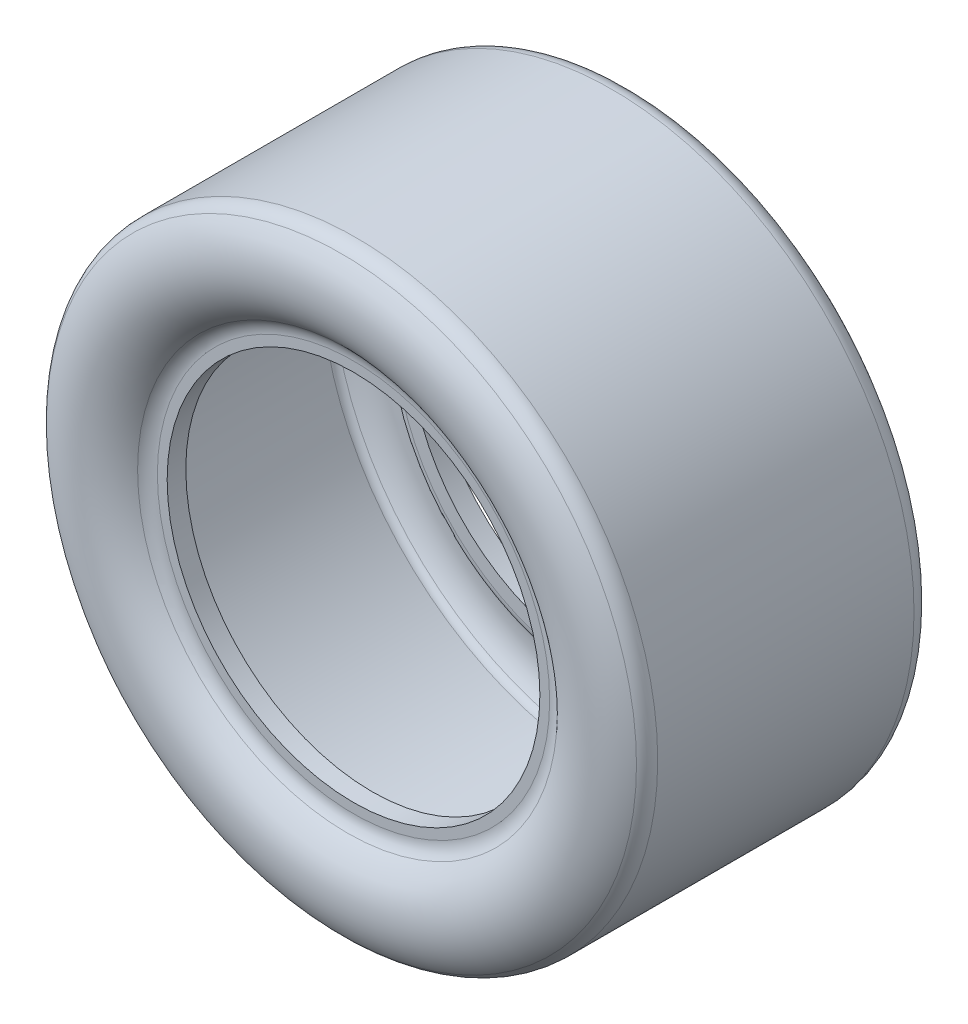
SolidWorks part; units mm, degrees
material "Tire Rubber"
ref_plane "X-Z Datum" through (0, 0, 0) normal (0, 0, 1) x (1, 0, 0)
ref_plane "X-Y Datum" through (0, 0, 0) normal (0, 1, 0) x (1, 0, 0)
ref_plane "Y-Z Plane" through (0, 0, 0) normal (1, 0, 0) x (0, 0, -1)
sketch "Sketch1" plane through (0, 0, 0) normal (1, 0, 0) x (0, 0, -1)
  line L0 (0, 0) -> (-132272.0706, 0) construction
  line L1 (-92.71, 205.74) -> (92.71, 205.74)
  line L2 (0, 0) -> (0, -132272.0706) construction
  line L4 (-88.9, 127) -> (-88.9, 139.7)
  line L5 (88.9, 127) -> (88.9, 139.7)
  line L6 (-88.9, 127) -> (-76.2, 127)
  line L8 (76.2, 127) -> (88.9, 127)
  line L9 (-76.2, 127) -> (-76.2, 136.7746)
  line L10 (76.2, 127) -> (76.2, 136.7746)
  line L11 (-86.5663, 197.8025) -> (86.5663, 197.8025)
  arc A2 (-92.71, 205.74) -> (-88.9, 139.7) centre (-64.4017, 174.2433) ccw
  arc A3 (92.71, 205.74) -> (88.9, 139.7) centre (64.4017, 174.2433) cw
  arc A4 (-91.5819, 195.3468) -> (-80.4384, 143.7974) centre (-64.4017, 174.2433) ccw
  arc A5 (-86.5663, 197.8025) -> (-91.5819, 195.3468) centre (-86.5663, 191.4525) ccw
  arc A6 (-76.2, 136.7746) -> (-80.4384, 143.7974) centre (-84.1375, 136.7746) ccw
  arc A7 (91.5819, 195.3468) -> (80.4384, 143.7974) centre (64.4017, 174.2433) cw
  arc A8 (86.5663, 197.8025) -> (91.5819, 195.3468) centre (86.5663, 191.4525) cw
  arc A9 (80.4384, 143.7974) -> (76.2, 136.7746) centre (84.1375, 136.7746) ccw
  point P7 (-106.68, 171.8041)
  dimension "D4" = 213.36
  dimension "D9" = 7.9375
  dimension "D10" = 6.35
  dimension "D11" = 7.9375
  dimension "D12" = 7.9375
  dimension "D1" = 185.42
  dimension "D2" = 411.48
  dimension "D3" = 12.7
  dimension "D5" = 177.8
  dimension "D6" = 254
  dimension "D7" = 12.7
  dimension "D8" = 7.9375
revolve "Revolve1" add sketch "Sketch1" angle 360 about L0
fillet "Fillet1" radius 12.7 4 edges at (-139.7, 0, -88.9) (-139.7, 0, 88.9) (-205.74, 0, -92.71) (-205.74, 0, 92.71)
ref_axis "Axis1" [suppressed] through (0, 0, 87.3303) along (0, 0, -1)
sketch "Sketch2" plane through (0, 0, 0) normal (0, 0, 1) x (1, 0, 0)
  circle A0 centre (0, 0) radius 205.74
  dimension "D1" = 411.48
extrude "Boss-Extrude1" [suppressed] add sketch "Sketch2" along normal mid plane 185.42
fillet "Fillet2" [suppressed] radius 25.4
sketch "Sketch3" plane through (0, 0, 0) normal (1, 0, 0) x (0, 0, -1)
  line L0 (0, 0) -> (0, 170833.7536) construction
  line L1 (0, 0) -> (-170833.7536, 0) construction
  line L2 (106.68, 205.74) -> (-106.68, 205.74)
  line L3 (-106.68, 205.74) -> (-106.68, 0)
  line L4 (106.68, 205.74) -> (106.68, 0)
  line L5 (106.68, 0) -> (-106.68, 0)
  point P7 (0, 205.74)
  dimension "D1" = 213.36
  dimension "D2" = 411.48
revolve "Revolve2" [suppressed] add sketch "Sketch3" angle 360 about L1
ref_plane "Plane1" through (0, 0, 0) normal (0, 0, 1) x (1, 0, 0)
sketch "Sketch4" plane through (0, 0, 0) normal (0, 0, 1) x (1, 0, 0)
  line L0 (0, 0) -> (0, 96.3997) construction
move or copy body "Body-Move/Copy2" [suppressed] bodies to move or copy 101
move or copy body "Body-Move/Copy1" [suppressed] bodies to move or copy 101
